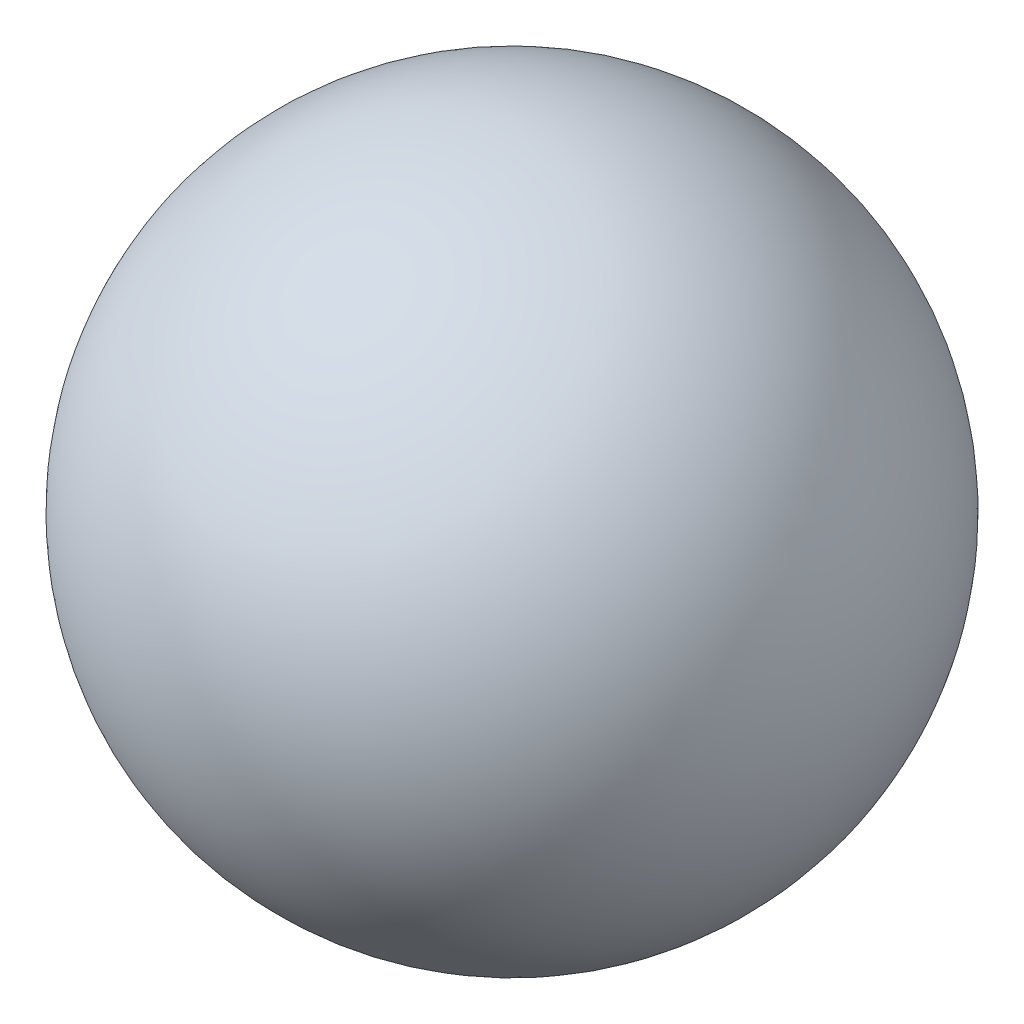
SolidWorks part; units mm, degrees
ref_plane "Front" through (0, 0, 0) normal (0, 0, 1) x (1, 0, 0)
ref_plane "Top" through (0, 0, 0) normal (0, 1, 0) x (1, 0, 0)
ref_plane "Right" through (0, 0, 0) normal (1, 0, 0) x (0, 0, -1)
sketch "Sketch1" plane through (0, 0, 0) normal (0, 1, 0) x (1, 0, 0)
  line L1 (0, 0) -> (200, 0)
  line L2 (0, 0) -> (0, 200)
  line L3 (0, 200) -> (200, 200)
  line L4 (200, 0) -> (200, 200)
  dimension "D1" = 200
extrude "Boss-Extrude1" add sketch "Sketch1" along normal blind 850
sketch "Sketch2" plane through (0, 850, 0) normal (0, 1, 0) x (1, 0, 0)
  line L0 (200, 0) -> (200, 200) construction
  line L1 (200, 200) -> (0, 200) construction
  line L2 (200, 0) -> (200, 200) construction
  line L3 (200, 200) -> (0, 200) construction
  line L4 (100, 161.5) -> (100, 100) construction
  circle A0 centre (100, 100) radius 61.5 construction
  circle A1 centre (100, 161.5) radius 3
  circle A2 centre (161.5, 100) radius 3
  circle A3 centre (100, 38.5) radius 3
  circle A4 centre (38.5, 100) radius 3
  point P4 (100, 200)
  point P7 (200, 100)
  point P10 (57.5076, 144.4595)
  point P11 (0, 0)
  point P12 (0, 0)
  point P19 (100, 100)
  point P20 (0, 0)
  dimension "D1" = 123
  dimension "D3" = 6
  dimension "D4" = 4
extrude "Cut-Extrude1" cut sketch "Sketch2" against normal blind 10
sketch "Sketch3" plane through (0, 850, 0) normal (0, 1, 0) x (1, 0, 0)
  line L0 (-1713, 100) -> (1913, 100)
  arc A0 (-1713, 100) -> (1913, 100) centre (100, 100) ccw
  dimension "D1" = 1813
revolve "Revolve1" add sketch "Sketch3" angle 360 about L0
